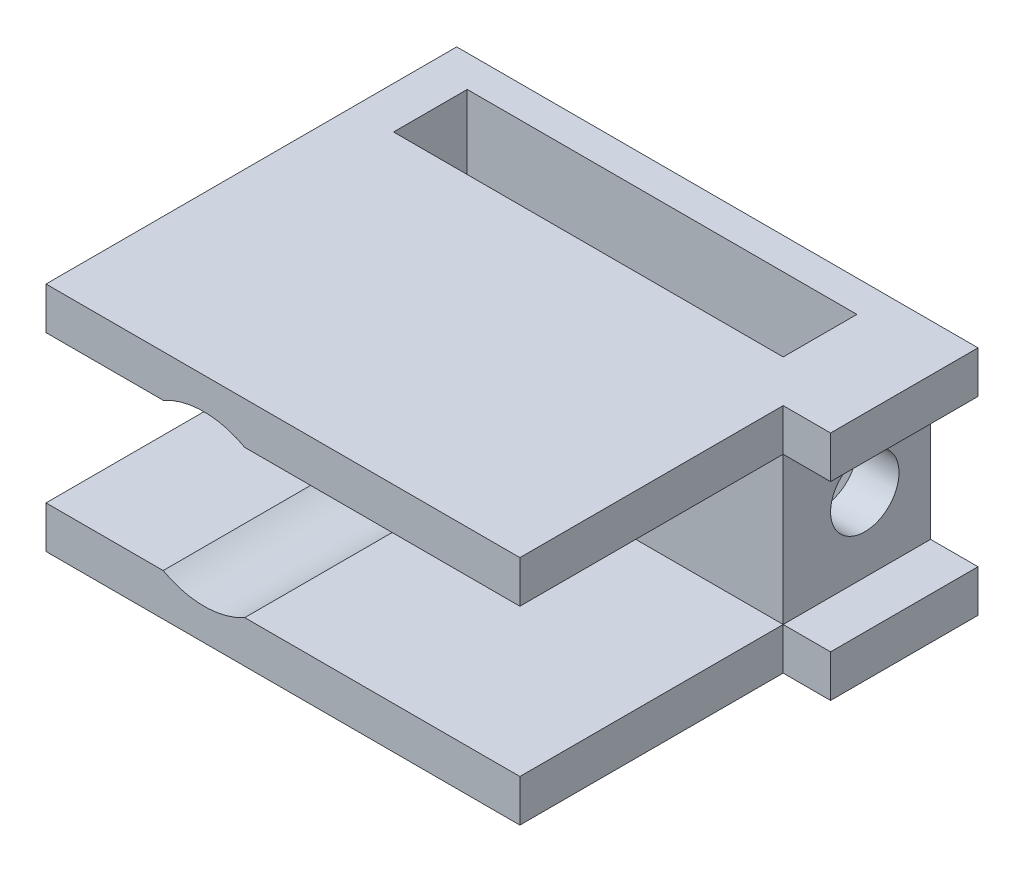
SolidWorks part; units mm, degrees
ref_plane "Plan de face" through (0, 0, 0) normal (0, 0, 1) x (1, 0, 0)
ref_plane "Plan de dessus" through (0, 0, 0) normal (0, 1, 0) x (1, 0, 0)
ref_plane "Plan de droite" through (0, 0, 0) normal (1, 0, 0) x (0, 0, -1)
sketch "Esquisse1" plane through (0, 0, 0) normal (0, 0, 1) x (1, 0, 0)
  line L1 (0, 0) -> (45, 0)
  line L2 (0, 0) -> (0, -22)
  line L3 (0, -22) -> (45, -22)
  line L4 (45, 0) -> (45, -22)
  dimension "D1" = 22
  dimension "D2" = 45
extrude "Boss.-Extru.1" add sketch "Esquisse1" along normal blind 4
sketch "Esquisse2" plane through (0, 0, 0) normal (0, 0, -1) x (-1, 0, 0)
  line L0 (0, 0) -> (0, -22) construction
  line L3 (0, -11) -> (-45, -11) construction
  line L4 (0, 0) -> (0, -22) construction
  line L5 (-45, -22) -> (-45, 0) construction
  circle A0 centre (-15, -11) radius 6.4
  point P14 (-15, -11)
  dimension "D1" = 12.8
  dimension "D2" = 15
extrude "Enlèv. mat.-Extru.1" cut sketch "Esquisse2" against normal up to surface (4 mm away) up to face at (22.5, -11, 4)
thread "Filetage1" pitch 1.5 method cut trim with start face yes trim with end face yes profile "Profil de filetage1" start angle 0, offset 1, length 0, pitch 1.4, diameter 12.8
ref_plane "Plan1" through (21.4, -11, -1) normal (0, -1, 0) x (1, 0, 0)
sketch "Profil de filetage1" plane through (21.4, -11, -1) normal (0, -1, 0) x (1, 0, 0)
  line L0 (0, 0) -> (0, 1.5) construction
  line L1 (0, 0) -> (0.8119, 0.4687)
  line L2 (0.8119, 0.4687) -> (0.8119, 0.6562)
  line L3 (0.8119, 0.6562) -> (0, 1.125)
  line L4 (0.8119, 0.5625) -> (0, 0.5625) construction
  line L11 (0, 0) -> (0, 1.125)
  point P2 (0, 0)
  dimension "Pitch" = 1.5
  dimension "Profile_Angle" = 60
  dimension "Profile_Land" = 0.1875
  dimension "Profile_Height" = 0.8119
sketch "Esquisse3" plane through (0, 0, 0) normal (0, 0, -1) x (-1, 0, 0)
  line L0 (0, -22) -> (-45, -22) construction
  line L1 (-45, 0) -> (-41, 0)
  line L2 (-45, 0) -> (-45, -22)
  line L3 (-45, -22) -> (-41, -22)
  line L4 (-41, 0) -> (-41, -22)
  line L6 (0, 0) -> (-4, 0)
  line L7 (0, 0) -> (0, -22)
  line L8 (0, -22) -> (-4, -22)
  line L9 (-4, 0) -> (-4, -22)
  dimension "D1" = 4
  dimension "D2" = 4
extrude "Boss.-Extru.2" add sketch "Esquisse3" along normal blind 10
sketch "Esquisse4" plane through (4, 0, 0) normal (1, 0, 0) x (0, 0, -1)
  line L0 (10, -22) -> (0, -22) construction
  line L1 (10, 0) -> (7, 0)
  line L2 (10, 0) -> (10, -22)
  line L3 (10, -22) -> (7, -22)
  line L4 (7, 0) -> (7, -22)
  dimension "D1" = 3
extrude "Boss.-Extru.3" add sketch "Esquisse4" along normal up to surface (37 mm away) up to face at (41, -11, -5)
sketch "Esquisse5" plane through (4, 0, 0) normal (1, 0, 0) x (0, 0, -1)
  line L0 (7, 0) -> (7, -22) construction
  line L1 (0, -11) -> (4.6746, -11) construction
  line L2 (0, 0) -> (0, -22) construction
  circle A0 centre (3.75, -11) radius 3.25
  dimension "D1" = 6.5
extrude "Enlèv. mat.-Extru.2" cut sketch "Esquisse5" against normal up to surface and the other way up to surface up to face at (0, -11, -3) other way up to face at (45, -11, -3)
sketch "Esquisse6" plane through (0, 0, 4) normal (0, 0, 1) x (1, 0, 0)
  line L0 (0, 0) -> (0, -22) construction
  line L1 (45, 0) -> (0, 0)
  line L2 (45, 0) -> (45, -4)
  line L3 (45, -4) -> (0, -4)
  line L4 (0, 0) -> (0, -4)
  line L6 (45, -22) -> (0, -22)
  line L7 (45, -22) -> (45, -18)
  line L8 (45, -18) -> (0, -18)
  line L9 (0, -22) -> (0, -18)
  dimension "D1" = 14
extrude "Boss.-Extru.4" add sketch "Esquisse6" along normal blind 25
sketch "Esquisse7" plane through (0, 0, 4) normal (0, 0, 1) x (1, 0, 0)
  circle A0 centre (15, -11) radius 8
  dimension "D1" = 16
extrude "Enlèv. mat.-Extru.4" cut sketch "Esquisse7" along normal up to surface (25 mm away) up to face at (22.5, -20, 29)
sketch "Esquisse8" plane through (45, 0, 0) normal (1, 0, 0) x (0, 0, -1)
  line L1 (10, -22) -> (-4, -22)
  line L2 (10, -22) -> (10, -18)
  line L3 (10, -18) -> (-4, -18)
  line L4 (-4, -22) -> (-4, -18)
  line L5 (-4, -4) -> (10, -4)
  line L6 (-4, -4) -> (-4, 0)
  line L7 (-4, 0) -> (10, 0)
  line L8 (10, -4) -> (10, 0)
extrude "Boss.-Extru.5" add sketch "Esquisse8" along normal blind 4.5
